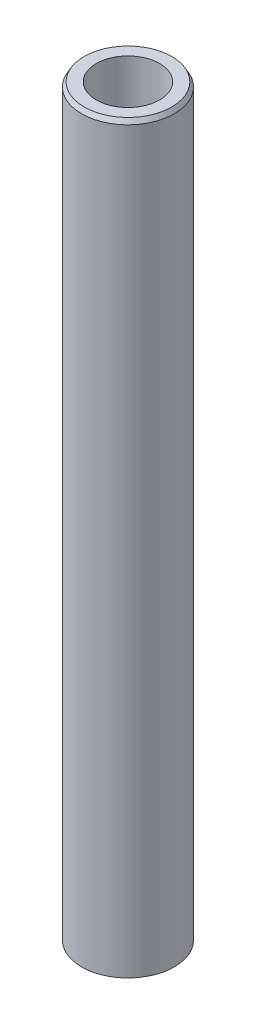
SolidWorks part; units mm, degrees
ref_plane "Front Plane" through (0, 0, 0) normal (0, 0, 1) x (1, 0, 0)
ref_plane "Top Plane" through (0, 0, 0) normal (0, 1, 0) x (1, 0, 0)
ref_plane "Right Plane" through (0, 0, 0) normal (1, 0, 0) x (0, 0, -1)
sketch "Sketch1" plane through (0, 0, 0) normal (0, 1, 0) x (1, 0, 0)
  circle A0 centre (0, 0) radius 27.5
  dimension "SHAFT_OD" = 55
extrude "Boss-Extrude1" add sketch "Sketch1" along normal blind 442.3021
sketch "Sketch2" plane through (0, 0, 0) normal (0, 1, 0) x (1, 0, 0)
  circle A0 centre (0, 0) radius 18.7576
  dimension "BORE_D" = 37.5152
extrude "Cut-Extrude1" cut sketch "Sketch2" along normal through all
chamfer "Chamfer1" distance 2.6895 angle 30 2 edges at (0, 442.3021, 27.5) (0, 0, 27.5) first distance on face at (0, 442.3021, 27.5) first distance on face at (0, 0, 18.7576)
